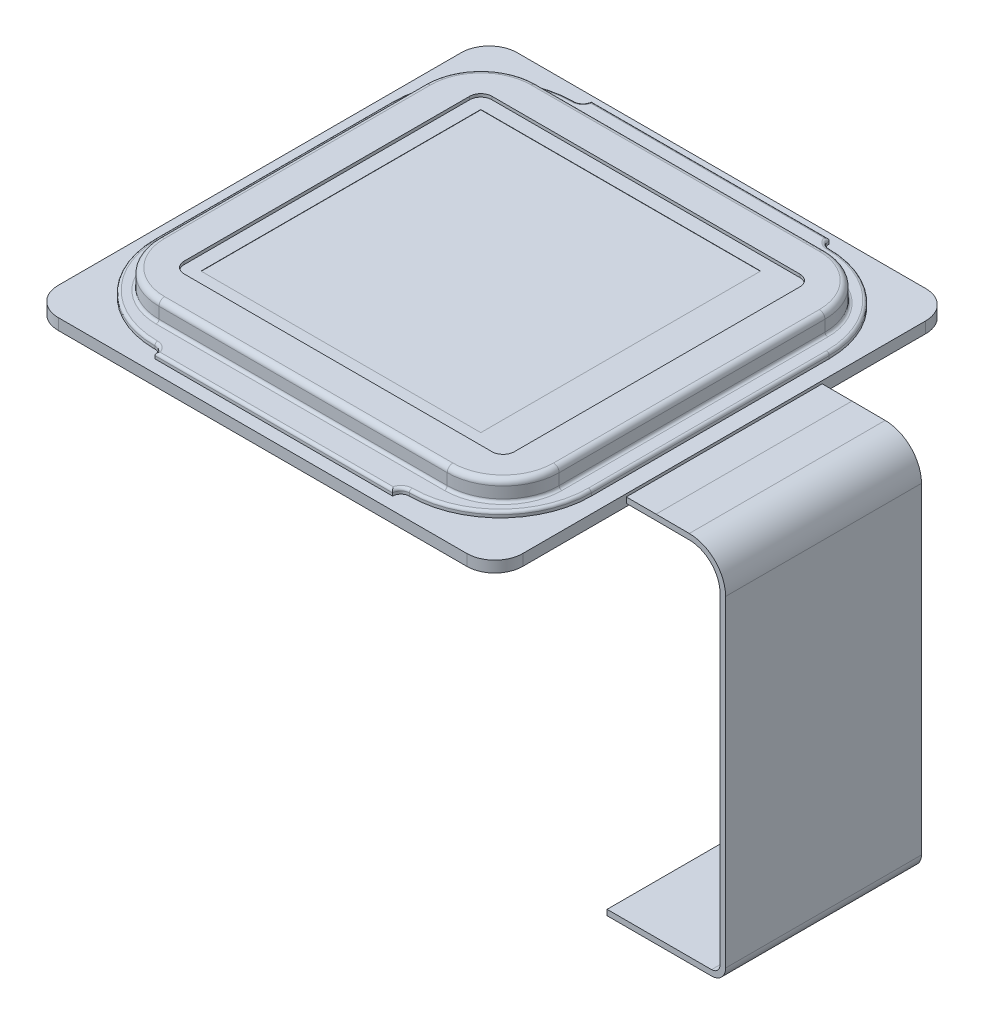
SolidWorks part; units mm, degrees
ref_plane "前视基准面" through (0, 0, 0) normal (0, 0, 1) x (1, 0, 0)
ref_plane "上视基准面" through (0, 0, 0) normal (0, 1, 0) x (1, 0, 0)
ref_plane "右视基准面" through (0, 0, 0) normal (1, 0, 0) x (0, 0, -1)
sketch "草图1" plane through (0, 0, 0) normal (0, 1, 0) x (1, 0, 0)
  line L0 (7.3, -8.2) -> (-7.3, -8.2)
  line L1 (8.3, -7.2) -> (8.3, 7.2)
  line L2 (7.3, 8.2) -> (-7.3, 8.2)
  line L3 (-8.3, -7.2) -> (-8.3, 7.2)
  line L4 (8.3, -8.2) -> (-8.3, 8.2) construction
  line L5 (8.3, 8.2) -> (-8.3, -8.2) construction
  line L6 (7.75, -4.2029) -> (7.75, 4.3)
  line L7 (-7.85, -4.2) -> (-7.85, 4.3)
  line L8 (7.8, -7.5) -> (-7.8, 7.5) construction
  line L9 (7.8, 7.5) -> (-7.8, -7.5) construction
  line L10 (5.15, -6.75) -> (-5.15, -6.75)
  line L11 (7.15, -4.75) -> (7.15, 4.75)
  line L12 (5.15, 6.75) -> (-5.15, 6.75)
  line L13 (-7.15, -4.75) -> (-7.15, 4.75)
  line L14 (7.15, -6.75) -> (-7.15, 6.75) construction
  line L15 (7.15, 6.75) -> (-7.15, -6.75) construction
  line L20 (5.5671, -5.5) -> (-5.5671, 5.5) construction
  line L21 (5.5671, 5.5) -> (-5.5671, -5.5) construction
  line L22 (-7.85, -9.45) -> (-7.85, 9.55) construction
  line L24 (5.5, -5.5) -> (-5.5, -5.5)
  line L25 (5.9, -5.1) -> (5.9, 5.1)
  line L26 (5.5, 5.5) -> (-5.5, 5.5)
  line L27 (4.2, -7.75) -> (-4.3, -7.75)
  line L28 (4.2, 7.85) -> (-4.3, 7.85)
  line L29 (-5.9, -5.1) -> (-5.9, 5.1)
  line L30 (5.9, -5.5) -> (-5.9, 5.5) construction
  line L31 (5.9, 5.5) -> (-5.9, -5.5) construction
  arc A0 (7.3, -8.2) -> (8.3, -7.2) centre (7.3, -7.2) ccw
  arc A1 (8.3, 7.2) -> (7.3, 8.2) centre (7.3, 7.2) ccw
  arc A2 (-7.3, -8.2) -> (-8.3, -7.2) centre (-7.3, -7.2) cw
  arc A3 (-7.3, 8.2) -> (-8.3, 7.2) centre (-7.3, 7.2) ccw
  arc A4 (4.5, -7.4529) -> (7.75, -4.2029) centre (4.5, -4.2029) ccw
  arc A5 (-4.6, -7.45) -> (-7.85, -4.2) centre (-4.6, -4.2) cw
  arc A6 (7.75, 4.3) -> (4.5, 7.55) centre (4.5, 4.3) ccw
  arc A7 (-4.6, 7.55) -> (-7.85, 4.3) centre (-4.6, 4.3) ccw
  arc A8 (5.15, -6.75) -> (7.15, -4.75) centre (5.15, -4.75) ccw
  arc A9 (-5.15, -6.75) -> (-7.15, -4.75) centre (-5.15, -4.75) cw
  arc A10 (7.15, 4.75) -> (5.15, 6.75) centre (5.15, 4.75) ccw
  arc A11 (-5.15, 6.75) -> (-7.15, 4.75) centre (-5.15, 4.75) ccw
  arc A16 (-4.6, 7.55) -> (-4.3, 7.85) centre (-4.6, 7.85) ccw
  arc A17 (4.5, 7.55) -> (4.2, 7.85) centre (4.5, 7.85) cw
  arc A18 (4.5, -7.4529) -> (4.2, -7.75) centre (4.5, -7.7529) ccw
  arc A19 (-4.6, -7.45) -> (-4.3, -7.75) centre (-4.6, -7.75) cw
  arc A20 (5.5, -5.5) -> (5.9, -5.1) centre (5.5, -5.1) ccw
  arc A21 (5.9, 5.1) -> (5.5, 5.5) centre (5.5, 5.1) ccw
  arc A22 (-5.5, 5.5) -> (-5.9, 5.1) centre (-5.5, 5.1) ccw
  arc A23 (-5.9, -5.1) -> (-5.5, -5.5) centre (-5.5, -5.1) ccw
  point P0 (0, 0)
  point P17 (0, 0)
  point P34 (0, 0)
  point P52 (0, 0)
  point P57 (0, 0)
  dimension "D3" = 1
  dimension "D4" = 3.25
  dimension "D5" = 2
  dimension "D6" = 11.8
  dimension "D12" = 0.3
  dimension "D13" = 0.3
  dimension "D17" = 0.4
  dimension "D1" = 16.6
  dimension "D2" = 16.4
  dimension "D7" = 15
  dimension "D8" = 13.5
  dimension "D9" = 11
  dimension "D10" = 15.6
  dimension "D11" = 14.3
  dimension "D14" = 11
  dimension "D15" = 3.25
  dimension "D16" = 0.3
  dimension "D18" = 3.25
  dimension "D20" = 0.7
extrude "凸台-拉伸1" add sketch "草图1" along normal blind 0.4 contours A19 A5 L7 A7 A16 L2 A3 L3 A2 L0 | A4 A18 L0 A0 L1 A1 L2 A17 A6 L6 region at (0, 0, 7.9667)
extrude "凸台-拉伸2" add sketch "草图1<3>" along normal blind 0.6 contours A5 A19 L0 A18 A4 L6 A6 A17 L2 A16 A7 L7 A11 L12 A10 L11 A8 L10 A9 L13 region at (6.6421, 0, 6.345)
sketch "草图1<3>" plane through (0, 0, 0) normal (0, 1, 0) x (1, 0, 0) same geometry as "草图1"
extrude "凸台-拉伸3" add sketch "草图1<4>" along normal blind 1.3 contours L12 A11 L13 A9 L10 A8 L11 A10 L25 region at (0, 0, 6.5533)
sketch "草图1<4>" plane through (0, 0, 0) normal (0, 1, 0) x (1, 0, 0) same geometry as "草图1"
extrude "凸台-拉伸4" add sketch "草图1<5>" along normal blind 1.19 contours L29 A23 L24 A20 L25 A21 L26 A22 region at (0, 0, 0)
sketch "草图1<5>" plane through (0, 0, 0) normal (0, 1, 0) x (1, 0, 0) same geometry as "草图1"
fillet "圆角1" radius 0.1 12 edges at (4.2889, 0.6, 7.5398) (4.2879, 0.6, -7.6379) (6.7981, 0.6, -6.5981) (7.75, 0.6, -0.0485) (-4.3879, 0.6, 7.5379) (-4.3879, 0.6, -7.6379) (-6.8981, 0.6, -6.5981) (-7.85, 0.6, -0.05) (6.7981, 0.6, 6.501) (-6.8981, 0.6, 6.4981) (-0.05, 0.6, -7.85) (-0.05, 0.6, 7.75)
fillet "圆角2" radius 0.1 8 edges at (6.5642, 0.6, 6.1642) (7.15, 0.6, 0) (6.5642, 0.6, -6.1642) (0, 0.6, -6.75) (-6.5642, 0.6, -6.1642) (-7.15, 0.6, 0) (-6.5642, 0.6, 6.1642) (0, 0.6, 6.75)
fillet "圆角3" radius 0.2 8 edges at (-6.5642, 1.3, 6.1642) (0, 1.3, 6.75) (6.5642, 1.3, 6.1642) (7.15, 1.3, 0) (6.5642, 1.3, -6.1642) (0, 1.3, -6.75) (-6.5642, 1.3, -6.1642) (-7.15, 1.3, 0)
ref_plane "基准面1" through (0, 0, -3.5) normal (0, 0, -1) x (-1, 0, 0)
sketch "草图2" plane through (0, 0, 8.2) normal (0, 0, 1) x (1, 0, 0)
  line L0 (8.3, 0) -> (9.3651, 0) construction
  line L1 (8.3, 0.3) -> (9.3651, 0.3)
  line L2 (11.5477, -1.006) -> (11.5477, -12.8945) construction
  line L5 (8.3, 0.1) -> (9.3651, 0.1)
  line L6 (8.3, 0.3) -> (8.3, 0.1)
  line L8 (11.8477, -1.006) -> (11.8477, -12.8945) construction
  line L9 (11.6477, -1.006) -> (11.6477, -12.8945) construction
  line L10 (11.8477, -1.006) -> (11.8477, -12.506)
  line L11 (11.6477, -1.006) -> (11.6477, -12.506)
  line L15 (11.3477, -12.806) -> (7.6132, -12.806)
  line L16 (11.3477, -13.006) -> (7.6132, -13.006)
  line L17 (11.3477, -13.006) -> (7.6132, -13.006) construction
  line L18 (7.6132, -13.006) -> (7.6132, -12.806)
  arc A0 (11.5477, -1.006) -> (10.5498, -0.006) centre (10.5477, -1.006) ccw construction
  arc A1 (11.8477, -1.006) -> (10.5505, 0.294) centre (10.5477, -1.006) ccw
  arc A2 (11.6477, -1.006) -> (10.5501, 0.094) centre (10.5477, -1.006) ccw
  arc A3 (11.8477, -12.506) -> (11.3477, -13.006) centre (11.3477, -12.506) cw
  arc A4 (11.6477, -12.506) -> (11.3477, -12.806) centre (11.3477, -12.506) cw
  spline S0 degree 3 poles (9.3651, 0) (9.7225, 0.0015) (10.3026, -0.0055) (10.5498, -0.006) knots 0 0 0 0 0.397595 0.397595 0.397595 0.397595 construction
  spline S1 degree 1 poles (9.3651, 0.3) (10.5505, 0.294) knots 0 0 1 1 construction
  spline S2 degree 3 poles (9.3651, 0.3) (9.4663, 0.3004) (9.6594, 0.3) (10.0044, 0.2978) (10.3337, 0.2952) (10.4714, 0.2942) (10.5505, 0.294) knots 0.000466 0.000466 0.000466 0.000466 0.099748 0.19903 0.298313 0.397595 0.397595 0.397595 0.397595
  spline S3 degree 1 poles (9.3651, 0.1) (10.5501, 0.094) knots 0 0 1 1 construction
  spline S4 degree 3 poles (10.5501, 0.094) (10.4705, 0.0942) (10.3317, 0.0952) (10.0024, 0.0978) (9.6575, 0.1) (9.4657, 0.1004) (9.3651, 0.1) knots 0.000157 0.000157 0.000157 0.000157 0.099516 0.198876 0.298235 0.397595 0.397595 0.397595 0.397595
  dimension "D1" = 1
  dimension "D4" = 0.5
  dimension "D5" = 11.5
  dimension "D2" = 0.3
  dimension "D3" = 0.1
ref_plane "基准面2" through (0, 0, 0) normal (0, 0, 1) x (1, 0, 0)
extrude "凸台-拉伸5" add sketch "草图2" along normal blind 3.5 and the other way blind 3.5 from surface starting at plane "基准面2"
sketch "草图3" plane through (0, 1.19, 0) normal (0, 1, 0) x (1, 0, 0)
  line L0 (5.5, -5.5) -> (-5.5, -5.5) construction
  line L1 (4.6, -5) -> (-5.4, -5)
  line L2 (4.6, -5) -> (4.6, 5)
  line L3 (4.6, 5) -> (-5.4, 5)
  line L4 (-5.4, -5) -> (-5.4, 5)
  line L5 (4.6, -5) -> (-5.4, 5) construction
  line L6 (4.6, 5) -> (-5.4, -5) construction
  line L8 (-5.9, -5.1) -> (-5.9, 5.1) construction
  point P0 (-0.4, 0)
  dimension "D1" = 10
  dimension "D2" = 0.5
  dimension "D3" = 0.5
extrude "切除-拉伸1" cut sketch "草图3" against normal blind 0.01
